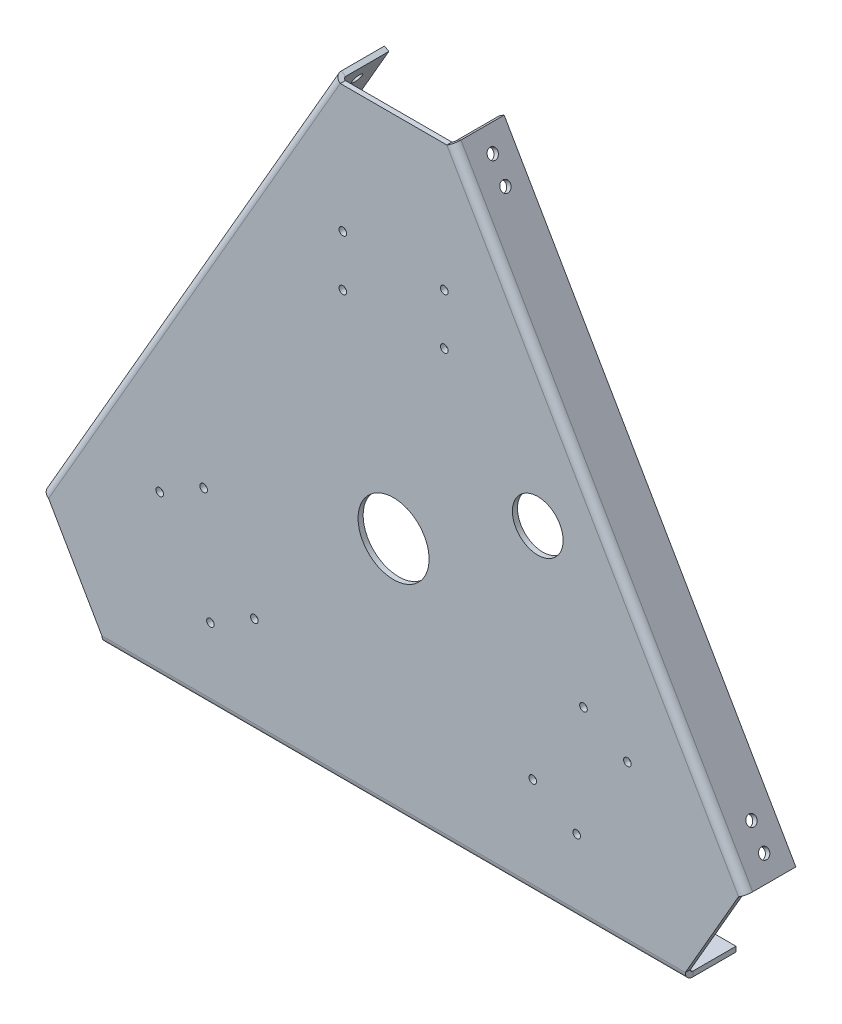
SolidWorks part; units mm, degrees
note: The reader was unsure of these and kept them because the rebuilt part matched: flange length of "Ребро-кромка6".
ref_plane "Спереди" through (0, 0, 0) normal (0, 0, 1) x (1, 0, 0)
ref_plane "Сверху" through (0, 0, 0) normal (0, 1, 0) x (1, 0, 0)
ref_plane "Справа" through (0, 0, 0) normal (1, 0, 0) x (0, 0, -1)
sketch "Эскиз10" plane through (0, 0, 0) normal (0, 0, 1) x (1, 0, 0)
  line L0 (0, 0) -> (-21, 36.3731)
  line L1 (-21, 36.3731) -> (94, 235.5589)
  line L2 (94, 235.5589) -> (136, 235.5589)
  line L3 (136, 235.5589) -> (251, 36.3731)
  line L4 (251, 36.3731) -> (230, 0)
  line L5 (230, 0) -> (0, 0)
  line L6 (-21, 36.3731) -> (218.4306, 174.6084) construction
  line L7 (0, 0) -> (239.3802, 138.2062) construction
  line L12 (-27.8347, 37.0459) -> (221.1942, 180.8227) construction
  line L13 (243.0289, 135.694) -> (-10.7713, -10.8376) construction
  line L20 (90, 29.8387) -> (94, 29.8387) construction
  line L21 (136, 24.636) -> (140, 24.636) construction
  line L40 (36.111, 37.4539) -> (-7.1903, 12.4539) construction
  line L41 (201.0385, 49.8372) -> (244.3397, 24.8372) construction
  circle A12 centre (171.8494, 123.466) radius 10
  dimension "D9" = 20
  dimension "D1" = 230
  dimension "D2" = 42
  dimension "D3" = 60
  dimension "D4" = 60
  dimension "D10" = 25
  dimension "D11" = 21
  dimension "D12" = 21
sheet metal parameters "Листовой металл3" thickness 2 parameters "D1"=0.7366
base flange "Базовая кромка3" sketch "Эскиз10" thickness 2 reverse thickness direction no parameters "D1"=0.7366
edge flange "Ребро-кромка6" sketch "Эскиз39" flange profiles "Эскиз39", "Эскиз40", "Эскиз41" flange angle 90 flange length 20 flange position bend outside bend radius 1 thickness 2 relief rectangular parameters "D6"=10, "D8"=1
sketch "Эскиз39" plane through (-31.5, 18.1865, -2) normal (-0.866, 0.5, 0) x (0.5, 0.866, 0)
  line L0 (251, 0) -> (21, 0) construction
  line L1 (251, 0) -> (21, 0)
  line L2 (21, 0) -> (21, 18)
  line L3 (21, 18) -> (251, 18)
  line L4 (251, 18) -> (251, 0)
sketch "Эскиз40" plane through (204, 117.7795, -2) normal (0.866, 0.5, 0) x (0.5, -0.866, 0)
  line L0 (94, 0) -> (-136, 0) construction
  line L1 (94, 0) -> (-136, 0)
  line L2 (-136, 0) -> (-136, 18)
  line L3 (-136, 18) -> (94, 18)
  line L4 (94, 18) -> (94, 0)
sketch "Эскиз41" plane through (0, 0, -2) normal (0, -1, 0) x (-1, 0, 0)
  line L0 (0, 0) -> (-230, 0) construction
  line L1 (0, 0) -> (-230, 0)
  line L2 (-230, 0) -> (-230, 18)
  line L3 (-230, 18) -> (0, 18)
  line L4 (0, 18) -> (0, 0)
bend "EdgeBend10" bend radius 1 bend angle 90 parameters "D5"=9
bend "EdgeBend11" bend radius 1 bend angle 90 parameters "D5"=10
bend "EdgeBend12" bend radius 1 bend angle 90 parameters "D5"=11
sketch "Эскиз47" plane through (-34.0981, 19.6865, 0) normal (-0.866, 0.5, 0) x (0, 0, 1)
  line L0 (-11.5, 21) -> (-11.5, 251) construction
  line L1 (-20, 21) -> (-3, 21) construction
  line L2 (-3, 251) -> (-20, 251) construction
  circle A0 centre (-11.5, 29) radius 2
  circle A1 centre (-11.5, 39) radius 2
  circle A2 centre (-11.5, 233) radius 2
  circle A3 centre (-11.5, 243) radius 2
  dimension "D1" = 4
  dimension "D4" = 4
  dimension "D2" = 10
  dimension "D3" = 8
  dimension "D5" = 10
  dimension "D6" = 8
extrude "Вырез-Вытянуть4" cut sketch "Эскиз47" against normal up to next normal cut yes
sketch "Эскиз50" plane through (206.5981, 119.2795, 0) normal (0.866, 0.5, 0) x (0, 0, -1)
  line L0 (11.5, -94) -> (11.5, 136) construction
  line L1 (3, -94) -> (20, -94) construction
  line L2 (20, 136) -> (3, 136) construction
  circle A0 centre (11.5, -86) radius 2
  circle A1 centre (11.5, -76) radius 2
  circle A2 centre (11.5, 118) radius 2
  circle A3 centre (11.5, 128) radius 2
  dimension "D3" = 4
  dimension "D1" = 8
  dimension "D2" = 10
  dimension "D4" = 8
  dimension "D5" = 10
extrude "Вырез-Вытянуть6" cut sketch "Эскиз50" against normal up to next normal cut yes
sketch "Эскиз51" plane through (0, -3, 0) normal (0, -1, 0) x (1, 0, 0)
  line L0 (230, -11.5) -> (0, -11.5) construction
  line L1 (230, -20) -> (230, -3) construction
  line L2 (0, -3) -> (0, -20) construction
  circle A0 centre (222, -11.5) radius 2
  circle A1 centre (212, -11.5) radius 2
  circle A2 centre (18, -11.5) radius 2
  circle A3 centre (8, -11.5) radius 2
  dimension "D3" = 4
  dimension "D1" = 10
  dimension "D2" = 8
  dimension "D4" = 10
  dimension "D5" = 8
extrude "Вырез-Вытянуть7" cut sketch "Эскиз51" against normal up to next normal cut yes
sketch "Эскиз52" plane through (0, 0, -2) normal (0, 0, -1) x (-1, 0, 0)
  line L0 (-115, 235.5589) -> (-115, -1) construction
  line L2 (0, -1) -> (-230, -1) construction
  line L3 (-240.5, 18.1865) -> (-36.5, 135.966) construction
  line L4 (-230, 0) -> (-251, 36.3731) construction
  line L5 (-94, 235.5589) -> (21, 36.3731) construction
  line L7 (-136, 235.5589) -> (-94, 235.5589) construction
  circle A0 centre (-115, 90.644) radius 14
  dimension "D1" = 28
extrude "Вырез-Вытянуть8" cut sketch "Эскиз52" against normal up to next normal cut yes
sketch "Эскиз53" plane through (0, 0, -2) normal (0, 0, -1) x (-1, 0, 0)
  line L0 (-40.1218, 70.507) -> (-22.8013, 60.507) construction
  line L1 (21, 36.3731) -> (0, 0) construction
  line L2 (10.5, 18.1865) -> (-115, 90.644) construction
  line L3 (-22.8013, 60.507) -> (-42.8013, 25.866) construction
  line L4 (-230, 0) -> (-251, 36.3731) construction
  line L5 (-240.5, 18.1865) -> (-115, 90.644) construction
  line L6 (-115, 90.644) -> (-115, 235.5589) construction
  line L7 (-136, 235.5589) -> (-94, 235.5589) construction
  line L8 (-42.8013, 25.866) -> (-60.1218, 35.866) construction
  line L9 (-60.1218, 35.866) -> (-40.1218, 70.507) construction
  line L10 (-95, 185.5589) -> (-95, 165.5589) construction
  line L11 (-95, 165.5589) -> (-135, 165.5589) construction
  line L12 (-135, 165.5589) -> (-135, 185.5589) construction
  line L13 (-135, 185.5589) -> (-95, 185.5589) construction
  line L14 (-207.1987, 60.507) -> (-189.8782, 70.507) construction
  line L15 (-189.8782, 70.507) -> (-169.8782, 35.866) construction
  line L16 (-169.8782, 35.866) -> (-187.1987, 25.866) construction
  line L17 (-187.1987, 25.866) -> (-207.1987, 60.507) construction
  circle A0 centre (-40.1218, 70.507) radius 1.5
  circle A1 centre (-22.8013, 60.507) radius 1.5
  circle A2 centre (-60.1218, 35.866) radius 1.5
  circle A3 centre (-42.8013, 25.866) radius 1.5
  circle A4 centre (-95, 185.5589) radius 1.5
  circle A5 centre (-95, 165.5589) radius 1.5
  circle A6 centre (-135, 185.5589) radius 1.5
  circle A7 centre (-135, 165.5589) radius 1.5
  circle A8 centre (-207.1987, 60.507) radius 1.5
  circle A9 centre (-189.8782, 70.507) radius 1.5
  circle A10 centre (-187.1987, 25.866) radius 1.5
  circle A11 centre (-169.8782, 35.866) radius 1.5
  point P19 (-50.1218, 53.1865)
  point P29 (-115, 165.5589)
  point P30 (0, 0)
  point P40 (-179.8782, 53.1865)
  dimension "D1" = 3
  dimension "D5" = 50
  dimension "D6" = 50
  dimension "D2" = 50
  dimension "D3" = 20
  dimension "D4" = 40
extrude "Вырез-Вытянуть9" cut sketch "Эскиз53" against normal blind 10 normal cut yes
flat pattern "Развертка3" [suppressed]
sketch "Сгиб-Линии3" plane through (0, 0, 0) normal (0, 0, 1) x (1, 0, 0)
  line L0 (252.1645, 37.0454) -> (137.1645, 236.2312) construction
  line L1 (0, -1.3446) -> (230, -1.3446) construction
  line L2 (252.1645, 37.0454) -> (137.1645, 236.2312) construction
  line L3 (92.8355, 236.2312) -> (-22.1645, 37.0454) construction
  line L4 (0, -1.3446) -> (230, -1.3446) construction
  line L5 (92.8355, 236.2312) -> (-22.1645, 37.0454) construction
sketch3d "Граничная рамка3" [suppressed]
  line L0 (-38.0514, -19.6892, 0) -> (268.0514, -19.6892, 0) construction
  line L1 (-38.0514, 245.4035, 0) -> (268.0514, 245.4035, 0) construction
  line L2 (-38.0514, -19.6892, 0) -> (-38.0514, 245.4035, 0) construction
  line L3 (268.0514, -19.6892, 0) -> (268.0514, 245.4035, 0) construction
bend of the flat pattern "Плоское состояние-<EdgeBend10>1"
bend of the flat pattern "Плоское состояние-<EdgeBend11>1"
bend of the flat pattern "Плоское состояние-<EdgeBend12>1"
